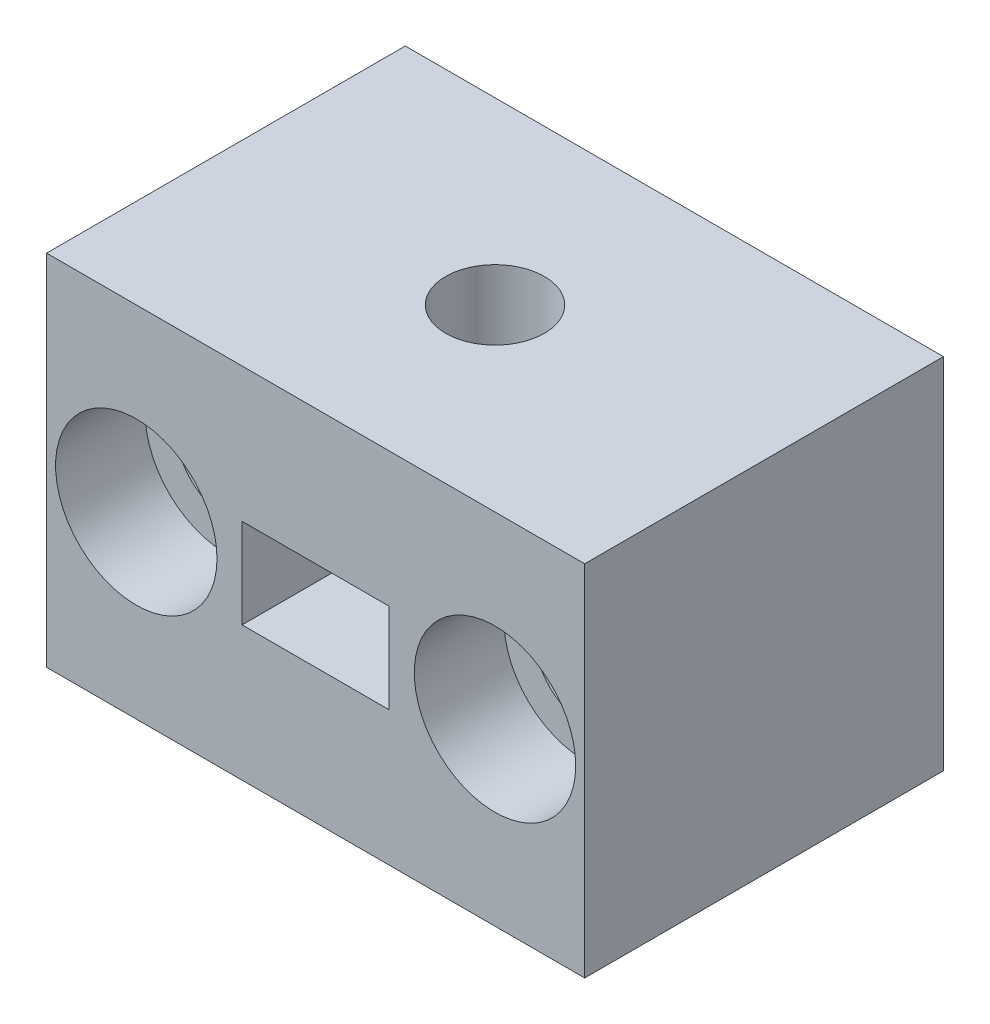
SolidWorks part; units mm, degrees
ref_plane "Front Plane" through (0, 0, 0) normal (0, 0, 1) x (1, 0, 0)
ref_plane "Top Plane" through (0, 0, 0) normal (0, 1, 0) x (1, 0, 0)
ref_plane "Right Plane" through (0, 0, 0) normal (1, 0, 0) x (0, 0, -1)
sketch "Sketch1" plane through (0, 0, 0) normal (0, 0, 1) x (1, 0, 0)
  line L1 (0, 0) -> (30, 0)
  line L2 (0, 0) -> (0, 20)
  line L3 (0, 20) -> (30, 20)
  line L4 (30, 0) -> (30, 20)
  dimension "D1" = 20
  dimension "D2" = 30
extrude "Boss-Extrude1" add sketch "Sketch1" along normal blind 20
sketch "Sketch2" plane through (0, 0, 20) normal (0, 0, 1) x (1, 0, 0)
  line L0 (30, 20) -> (0, 20) construction
  line L1 (0, 20) -> (0, 0) construction
  line L2 (30, 0) -> (30, 20) construction
  line L4 (10.9, 7.5) -> (19.1, 7.5)
  line L5 (10.9, 7.5) -> (10.9, 12.5)
  line L6 (10.9, 12.5) -> (19.1, 12.5)
  line L7 (19.1, 7.5) -> (19.1, 12.5)
  circle A0 centre (5, 10) radius 2.75
  circle A1 centre (25, 10) radius 2.75
  dimension "D1" = 5.5
  dimension "D2" = 5.5
  dimension "D3" = 10
  dimension "D4" = 10
  dimension "D5" = 5
  dimension "D6" = 5
  dimension "D7" = 5
  dimension "D8" = 8.2
  dimension "D9" = 10.9
  dimension "D10" = 7.5
extrude "Cut-Extrude1" cut sketch "Sketch2" against normal through all
sketch "Sketch3" plane through (0, 20, 0) normal (0, 1, 0) x (1, 0, 0)
  line L0 (0, -20) -> (0, 0) construction
  line L1 (30, 0) -> (0, 0) construction
  circle A0 centre (15, -10) radius 2.75
  dimension "D1" = 5.5
  dimension "D2" = 15
  dimension "D3" = 10
extrude "Cut-Extrude2" cut sketch "Sketch3" against normal through all
sketch "Sketch4" plane through (0, 7.5, 0) normal (0, 1, 0) x (1, 0, 0)
  line L0 (19.1, -7.5) -> (15.1, -5.1339)
  line L1 (19.1, 0) -> (19.1, -20) construction
  line L2 (15.1, -5.1339) -> (10.9, -7.5)
  line L3 (10.9, 0) -> (10.9, -20) construction
  line L8 (10.9, -20) -> (19.1, -20)
  line L9 (19.1, -20) -> (19.1, 0)
  line L10 (19.1, 0) -> (10.9, 0)
  line L11 (10.9, 0) -> (10.9, -20)
  line L13 (19.1, -7.5) -> (19.1, 0)
  line L14 (19.1, 0) -> (10.9, 0)
  line L15 (10.9, 0) -> (10.9, -7.5)
  point P4 (10.9, -10)
  point P9 (19.1, -10)
  dimension "D1" = 2.5
  dimension "D2" = 2.5
  dimension "D3" = 120
  dimension "D4" = 4
  dimension "D5" = 0
extrude "Boss-Extrude2" add sketch "Sketch4" along normal up to next
sketch "Sketch5" plane through (0, 0, 0) normal (0, 0, -1) x (-1, 0, 0)
  line L0 (-30, 20) -> (0, 20) construction
  line L1 (-19, 7) -> (-11, 7)
  line L2 (-19, 7) -> (-19, 13)
  line L3 (-19, 13) -> (-11, 13)
  line L4 (-11, 7) -> (-11, 13)
  line L5 (-30, 0) -> (-30, 20) construction
  dimension "D1" = 6
  dimension "D2" = 8
  dimension "D3" = 7
  dimension "D4" = 11
extrude "Boss-Extrude3" add sketch "Sketch5" along normal blind 3
sketch "Sketch6" plane through (0, 0, 20) normal (0, 0, 1) x (1, 0, 0)
  circle A0 centre (5, 10) radius 4.5
  circle A1 centre (25, 10) radius 4.5
  dimension "D1" = 9
  dimension "D2" = 9
extrude "Cut-Extrude3" cut sketch "Sketch6" against normal blind 5
